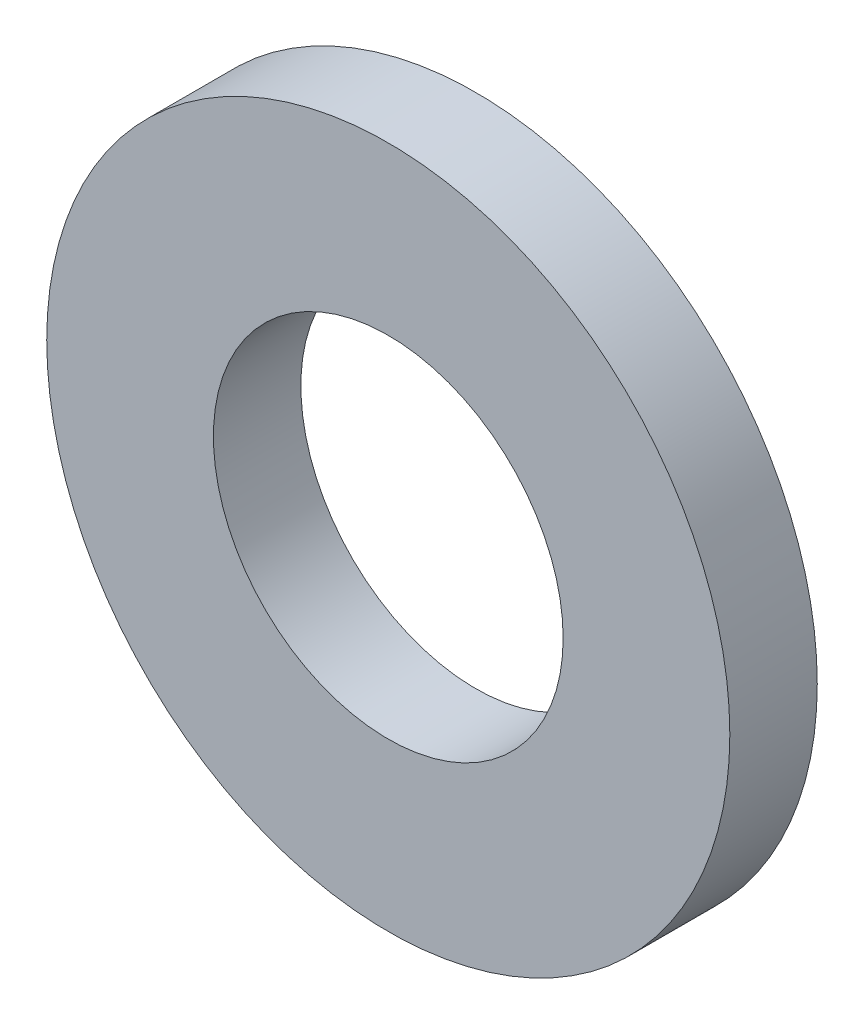
SolidWorks part; units mm, degrees
ref_plane "Front Plane" through (0, 0, 0) normal (0, 0, 1) x (1, 0, 0)
ref_plane "Top Plane" through (0, 0, 0) normal (0, 1, 0) x (1, 0, 0)
ref_plane "Right Plane" through (0, 0, 0) normal (1, 0, 0) x (0, 0, -1)
sketch "Sketch1" plane through (0, 0, 0) normal (0, 0, 1) x (1, 0, 0)
  circle A0 centre (0, 0) radius 6.25
  circle A1 centre (0, 0) radius 3.2
  point P4 (0, -3.2)
  dimension "ID" = 6.4
  dimension "OD" = 12.5
extrude "Boss-Extrude1" add sketch "Sketch1" along normal mid plane 1.6
ref_axis "Center Axis 1" through (0, 0, 0.8) along (0, 0, -1)
ref_plane "Contact Plane 1" through (0, 0, 0.8) normal (0, 0, 1) x (1, 0, 0)
ref_plane "Contact Plane 2" through (0, 0, -0.8) normal (0, 0, -1) x (-1, 0, 0)
